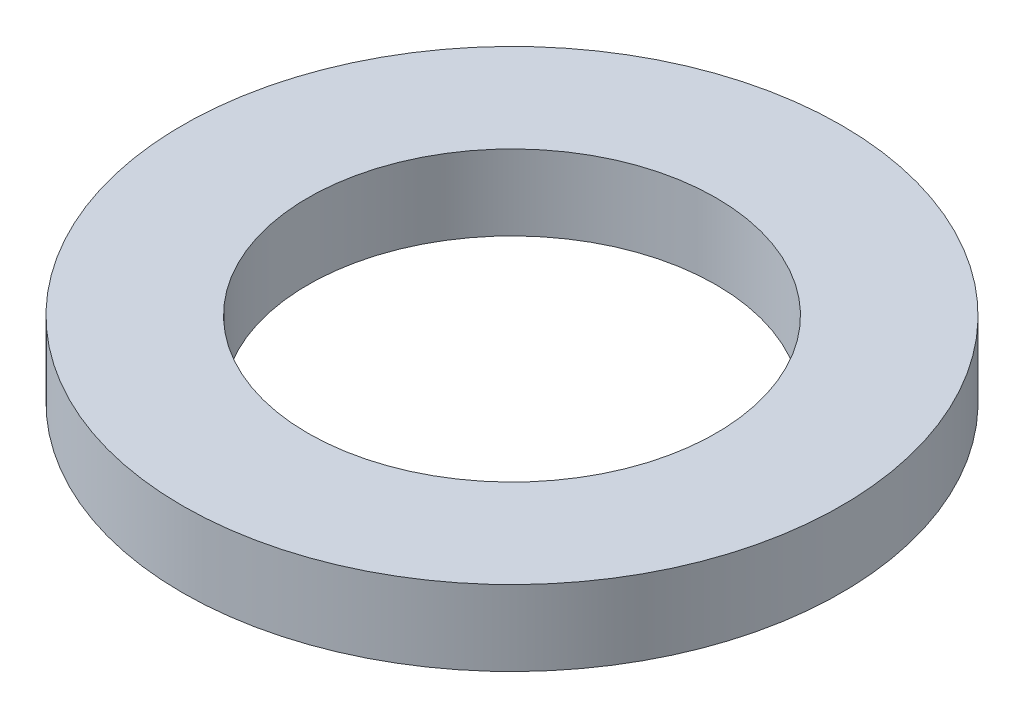
SolidWorks part; units mm, degrees
ref_plane "Front Plane" through (0, 0, 0) normal (0, 0, 1) x (1, 0, 0)
ref_plane "Top Plane" through (0, 0, 0) normal (0, 1, 0) x (1, 0, 0)
ref_plane "Right Plane" through (0, 0, 0) normal (1, 0, 0) x (0, 0, -1)
sketch "Sketch1" plane through (0, 0, 0) normal (0, 1, 0) x (1, 0, 0)
  circle A0 centre (0, 0) radius 52.5
  dimension "FLANGE_OD" = 105
extrude "Boss-Extrude1" add sketch "Sketch1" along normal blind 12
sketch "Sketch2" plane through (0, 0, 0) normal (0, 1, 0) x (1, 0, 0)
  circle A0 centre (0, 0) radius 32.5
  dimension "BORE_D" = 65
extrude "Cut-Extrude1" cut sketch "Sketch2" along normal through all
sketch "Sketch3" plane through (0, 12, 0) normal (0, 1, 0) x (1, 0, 0)
  circle A0 centre (0, 0) radius 21.0157 construction
  circle A1 centre (-21.0157, 0) radius 2.5339
  dimension "BOLT_D" = 5.0678
  dimension "BOLT_PCD" = 42.0315
extrude "Cut-Extrude2" cut sketch "Sketch3" against normal blind 8.5693 rebuild error yes
pattern_circular "CirPattern1" count 6 over 360 rebuild error yes
